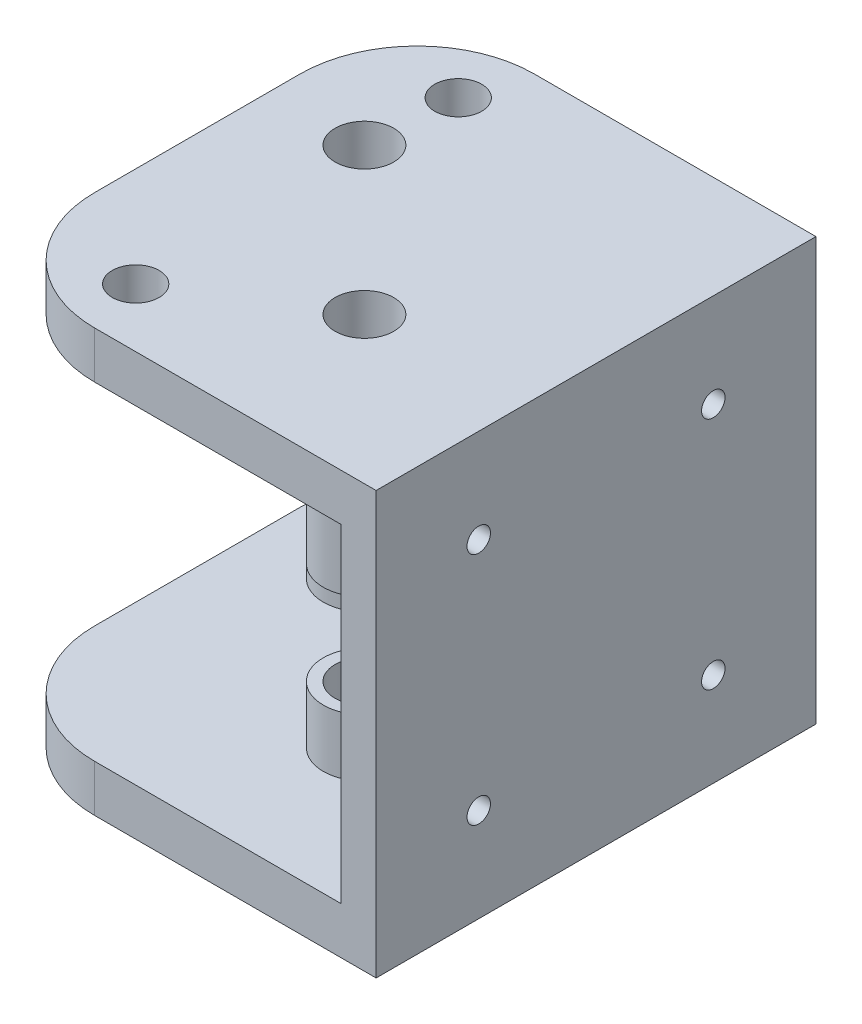
SolidWorks part; units mm, degrees
ref_plane "Front Plane" through (0, 0, 0) normal (0, 0, 1) x (1, 0, 0)
ref_plane "Top Plane" through (0, 0, 0) normal (0, 1, 0) x (1, 0, 0)
ref_plane "Right Plane" through (0, 0, 0) normal (1, 0, 0) x (0, 0, -1)
sketch "TopSketch1" plane through (0, 0, 0) normal (0, 1, 0) x (1, 0, 0)
  line L1 (0, 0) -> (34, 0)
  line L2 (0, 0) -> (0, 37.5)
  line L3 (0, 37.5) -> (34, 37.5)
  line L4 (34, 0) -> (34, 37.5)
  circle A0 centre (8.5, 32.5) radius 2
  circle A1 centre (8.5, 5) radius 2
  circle A2 centre (20.5, 12.5) radius 2.5
  circle A3 centre (8, 25) radius 2.5
  dimension "D7" = 4
  dimension "D8" = 5
  dimension "D2" = 12.5
  dimension "D3" = 12.5
  dimension "D4" = 5
  dimension "D5" = 5
  dimension "D10" = 37.5
  dimension "D9" = 12.5
  dimension "D12" = 13.5
  dimension "D6" = 25.5
  dimension "D11" = 8
  dimension "D13" = 12.5
extrude "Boss-Extrude1" add sketch "TopSketch1" along normal blind 4
sketch "TopLeftRiser" plane through (0, 0, 0) normal (0, -1, 0) x (1, 0, 0)
  line L0 (5.75, -27.681) -> (5.75, -37.5)
  line L1 (34, -37.5) -> (0, -37.5) construction
  line L2 (5.75, -37.5) -> (10.25, -37.5)
  line L3 (10.25, -37.5) -> (10.25, -27.681)
  arc A0 (10.25, -27.681) -> (5.75, -27.681) centre (8, -25) ccw
  circle A1 centre (8, -25) radius 2.5 construction
  circle A2 centre (8, -25) radius 2.5
  point P12 (8, -37.5)
  dimension "D1" = 7
  dimension "D2" = 4.5
extrude "TopLeftRiserBoss-Extrude2" add sketch "TopLeftRiser" along normal blind 4.9
sketch "TopRightRiser" plane through (0, 0, 0) normal (0, -1, 0) x (1, 0, 0)
  line L0 (18.25, -15.181) -> (18.25, -37.5)
  line L1 (34, -37.5) -> (10.25, -37.5) construction
  line L2 (18.25, -37.5) -> (22.75, -37.5)
  line L3 (22.75, -37.5) -> (22.75, -15.181)
  line L4 (5.75, -37.5) -> (10.25, -37.5) construction
  circle A0 centre (20.5, -12.5) radius 2.5
  circle A1 centre (20.5, -12.5) radius 2.5 construction
  arc A2 (22.75, -15.181) -> (18.25, -15.181) centre (20.5, -12.5) ccw
  arc A3 (10.25, -27.681) -> (5.75, -27.681) centre (8, -25) ccw construction
  point P15 (20.5, -37.5)
extrude "topRightRiserBoss-Extrude3" add sketch "TopRightRiser" along normal blind 14.4
sketch "MidWallSketch3" plane through (0, 0, 0) normal (0, -1, 0) x (1, 0, 0)
  line L1 (0, -34.5) -> (10.25, -34.5)
  line L2 (0, -34.5) -> (0, -37.5)
  line L3 (0, -37.5) -> (10.25, -37.5)
  line L4 (10.25, -34.5) -> (10.25, -37.5)
  line L5 (18.25, -34.5) -> (22.75, -34.5)
  line L6 (18.25, -34.5) -> (18.25, -37.5)
  line L7 (18.25, -37.5) -> (22.75, -37.5)
  line L8 (22.75, -34.5) -> (22.75, -37.5)
  line L9 (34, 0) -> (34, -37.5)
  line L10 (34, -37.5) -> (31, -37.5)
  line L11 (31, -37.5) -> (31, 0)
  line L14 (10.25, -37.5) -> (10.25, -27.681) construction
  line L15 (0, -37.5) -> (0, 0) construction
  line L16 (34, -37.5) -> (0, -37.5) construction
  line L17 (31, 0) -> (34, 0)
  line L19 (34, 0) -> (34, -37.5) construction
  line L20 (0, 0) -> (34, 0) construction
  line L21 (22.75, -37.5) -> (22.75, -15.181) construction
  line L22 (18.25, -15.181) -> (18.25, -37.5) construction
  dimension "D1" = 3
extrude "WallBoss-Extrude4" add sketch "MidWallSketch3" along normal blind 28
sketch "BottomSketch4" plane through (0, -28, 0) normal (0, -1, 0) x (1, 0, 0)
  line L0 (0, 0) -> (34, 0) construction
  line L1 (0, 0) -> (34, 0)
  line L2 (0, 0) -> (0, -37.5)
  line L3 (0, -37.5) -> (34, -37.5)
  line L4 (34, 0) -> (34, -37.5)
  line L5 (34, 0) -> (34, -37.5) construction
  line L6 (34, -37.5) -> (0, -37.5) construction
extrude "BottomBoss-Extrude5" add sketch "BottomSketch4" along normal blind 4
sketch "LowerLeftRiser" plane through (0, -28, 0) normal (0, 1, 0) x (1, 0, 0)
  line L0 (5.75, 27.681) -> (5.75, 34.5)
  line L1 (5.75, 34.5) -> (10.25, 34.5)
  line L2 (10.25, 34.5) -> (10.25, 27.681)
  line L3 (5.75, 34.5) -> (10.25, 34.5) construction
  line L4 (5.75, 27.681) -> (5.75, 34.5) construction
  line L5 (10.25, 34.5) -> (10.25, 27.681) construction
  circle A0 centre (8, 25) radius 2.5
  arc A1 (5.75, 27.681) -> (10.25, 27.681) centre (8, 25) ccw
  circle A2 centre (8, 25) radius 2.5 construction
  arc A3 (5.75, 27.681) -> (10.25, 27.681) centre (8, 25) ccw construction
extrude "LowerLeftRiserBoss-Extrude6" add sketch "LowerLeftRiser" along normal blind 14.4
sketch "LowerRightRiser" plane through (0, -28, 0) normal (0, 1, 0) x (1, 0, 0)
  line L0 (18.25, 15.181) -> (18.25, 34.5)
  line L1 (18.25, 34.5) -> (22.75, 34.5)
  line L2 (22.75, 34.5) -> (22.75, 15.181)
  line L3 (18.25, 34.5) -> (22.75, 34.5) construction
  line L4 (18.25, 15.181) -> (18.25, 34.5) construction
  line L5 (22.75, 34.5) -> (22.75, 15.181) construction
  circle A0 centre (20.5, 12.5) radius 2.5
  circle A1 centre (20.5, 12.5) radius 2.5 construction
  arc A2 (18.25, 15.181) -> (22.75, 15.181) centre (20.5, 12.5) ccw
  arc A3 (18.25, 15.181) -> (22.75, 15.181) centre (20.5, 12.5) ccw construction
extrude "LowerRightRiserBoss-Extrude7" add sketch "LowerRightRiser" along normal blind 4.9
fillet "Fillet1" radius 10 3 edges at (0, -30, 0) (0, 2, 0) (0, -14, -37.5)
sketch "GBMountingHolesSketch7" plane through (34, 0, 0) normal (1, 0, 0) x (0, 0, -1)
  line L0 (37.5, 4) -> (37.5, -32) construction
  line L1 (0, 4) -> (37.5, 4) construction
  line L2 (37.5, -32) -> (0, -32) construction
  line L3 (0, 4) -> (0, -32) construction
  circle A0 centre (8.75, -4) radius 1
  circle A1 centre (8.75, -24) radius 1
  circle A2 centre (28.75, -24) radius 1
  circle A3 centre (28.75, -4) radius 1
  dimension "D7" = 2
  dimension "D1" = 20
  dimension "D2" = 8.75
  dimension "D3" = 8
  dimension "D4" = 20
  dimension "D5" = 8
  dimension "D6" = 8.75
sketch "TopLeftInset" plane through (0, -4.9, 0) normal (0, -1, 0) x (1, 0, 0)
  line L0 (5.75, -27.681) -> (5.75, -34.5)
  line L1 (5.75, -34.5) -> (10.25, -34.5)
  line L2 (10.25, -34.5) -> (10.25, -27.681)
  line L3 (10.25, -34.5) -> (5.75, -34.5) construction
  line L4 (5.75, -34.5) -> (5.75, -27.681) construction
  line L5 (10.25, -27.681) -> (10.25, -34.5) construction
  arc A0 (5.75, -27.681) -> (10.25, -27.681) centre (8, -25) ccw
  arc A1 (10.25, -27.681) -> (5.75, -27.681) centre (8, -25) ccw construction
extrude "TopLeftInsetCut-Extrude1" cut sketch "TopLeftInset" against normal blind 1
sketch "TopRightInset" plane through (0, -14.4, 0) normal (0, -1, 0) x (1, 0, 0)
  line L0 (18.25, -15.181) -> (18.25, -34.5)
  line L1 (18.25, -34.5) -> (22.75, -34.5)
  line L2 (22.75, -34.5) -> (22.75, -15.181)
  line L3 (22.75, -34.5) -> (18.25, -34.5) construction
  line L4 (18.25, -34.5) -> (18.25, -15.181) construction
  line L5 (22.75, -15.181) -> (22.75, -34.5) construction
  arc A0 (18.25, -15.181) -> (22.75, -15.181) centre (20.5, -12.5) ccw
  arc A1 (22.75, -15.181) -> (18.25, -15.181) centre (20.5, -12.5) ccw construction
extrude "TopRightInsetCut-Extrude2" cut sketch "TopRightInset" against normal blind 1
sketch "LowerLeftInset" plane through (0, -13.6, 0) normal (0, 1, 0) x (1, 0, 0)
  line L0 (5.75, 27.681) -> (5.75, 34.5)
  line L1 (5.75, 34.5) -> (10.25, 34.5)
  line L2 (10.25, 34.5) -> (10.25, 27.681)
  line L3 (5.75, 34.5) -> (10.25, 34.5) construction
  line L4 (5.75, 27.681) -> (5.75, 34.5) construction
  line L5 (10.25, 34.5) -> (10.25, 27.681) construction
  arc A0 (10.25, 27.681) -> (5.75, 27.681) centre (8, 25) ccw
  arc A1 (5.75, 27.681) -> (10.25, 27.681) centre (8, 25) ccw construction
extrude "LowerLeftInsetCut-Extrude3" cut sketch "LowerLeftInset" against normal blind 1
sketch "LowerRightInset" plane through (0, -23.1, 0) normal (0, 1, 0) x (1, 0, 0)
  line L0 (18.25, 15.181) -> (18.25, 34.5)
  line L1 (18.25, 34.5) -> (22.75, 34.5)
  line L2 (22.75, 34.5) -> (22.75, 15.181)
  line L3 (18.25, 34.5) -> (22.75, 34.5) construction
  line L4 (18.25, 15.181) -> (18.25, 34.5) construction
  line L5 (22.75, 34.5) -> (22.75, 15.181) construction
  arc A2 (22.75, 15.181) -> (18.25, 15.181) centre (20.5, 12.5) ccw
  arc A3 (18.25, 15.181) -> (22.75, 15.181) centre (20.5, 12.5) ccw construction
extrude "LowerRightInsetCut-Extrude4" cut sketch "LowerRightInset" against normal blind 1
extrude "GBMountingHolesCut-Extrude5" cut sketch "GBMountingHolesSketch7" against normal blind 3
sketch "PushPinHoleSketch1" plane through (0, -32, 0) normal (0, -1, 0) x (1, 0, 0)
  circle A0 centre (20.5, -12.5) radius 1
  circle A1 centre (8, -25) radius 1
  circle A2 centre (8, -25) radius 2.5 construction
  circle A3 centre (20.5, -12.5) radius 2.5 construction
  dimension "D1" = 2
extrude "PushPinHoleCut-Extrude1" cut sketch "PushPinHoleSketch1" against normal through all
sketch "BottomLeftMountHoleAccessSketch1" plane through (5.75, 0, 0) normal (-1, 0, 0) x (0, 0, 1)
  circle A0 centre (-28.75, -24) radius 1
  dimension "D1" = 2
extrude "BottomLeftMountHoleAccessCut-Extrude2" cut sketch "BottomLeftMountHoleAccessSketch1" against normal blind 15 and the other way blind 10
sketch "TopLeftMountHoleAccessSketch2" plane through (18.25, 0, 0) normal (-1, 0, 0) x (0, 0, 1)
  circle A0 centre (-28.75, -4) radius 1
  circle A1 centre (-28.75, -24) radius 1 construction
extrude "TopLeftMountHoleAccessCut-Extrude3" cut sketch "TopLeftMountHoleAccessSketch2" against normal blind 5 and the other way through all
equation "\"GABDepth\"= \"GABDistanceFromBackToFirstPulley\" + \"GABPulleyDDistanceBetween\" + \"GABDistanceFromPulleyToFront\""
equation "\"GABWidth\"= \"StandardWallThickness\" + \"GABDistanceFromLSideToPulley\" + \"GABPulleyWDistanceBetween\" + \"GABDistanceFromPulleyToRSide\""
equation "\"GABLowerHeight\"= 4mm"
equation "\"GABUpperHeight\"= 4mm"
equation "\"GABMidWallHeight\"= 28mm'Must equal 28 or changes alignment"
equation "\"StandardWallThickness\"= 3mm"
equation "\"GABMidShortRiserHeight\"= \"GABMidWallHeight\" / 2 - \"20TGT2PulleyWidth\"'Equals 5.3"
equation "\"LinearGBMountHolesXDistance\"= 20mm'Spec"
equation "\"GABHeight\"= \"GABLowerHeight\" + \"GABMidWallHeight\" + \"GABUpperHeight\""
equation "\"GBMountingHoleDiameter\"= 2mm"
equation "\"GABMidLongRiserHeight\"= \"GABMidWallHeight\" - \"GABMidShortRiserHeight\" - \"20TGT2PulleyWidth\"'Equals 14"
equation "\"GABLRClampHoleOffsetFromSide\"= 5mm"
equation "\"GABDistanceFromBackToFirstPulley\"= 13.5mm"
equation "\"GABPulleyDDistanceBetween\"= 12.5mm'From the100"
equation "\"GABPulleyWDistanceBetween\"= 14.5mm'From the100"
equation "\"GABDistanceFromPulleyToFront\"= 8mm"
equation "\"GABDistanceFromLSideToPulley\"= 9.5mm + \"StandardWallThickness\""
equation "\"GABDistanceFromPulleyToRSide\"= 7.5mm"
equation "\"GABDistanceToFrontClampHoles\"= 8.5mm"
equation "\"SteelShaft5mmHoleDiameter\"= 5mm"
equation "\"20TGT2PulleyWidth\"= 8.7mm'The STL of the Pulley in the diagram is a bit larger"
equation "\"7mmx1mmSpacerDiameter\"= 7mm"
equation "\"7mmx1mmSpacerHeight\"= 1mm"
equation "\"GABRiserBossOffset\" = 0.4mm'Aligns Pulleys inside edges to be 2.5mm (.5mm apart top to bottom)"
equation "\"D2@TopSketch1\" = \"GABPulleyDDistanceBetween\""
equation "\"D3@TopSketch1\" = \"GABPulleyDDistanceBetween\""
equation "\"D4@TopSketch1\" = \"GABLRClampHoleOffsetFromSide\""
equation "\"D5@TopSketch1\" = \"GABLRClampHoleOffsetFromSide\""
equation "\"D8@TopSketch1\" = \"SteelShaft5mmHoleDiameter\""
equation "\"D10@TopSketch1\" = \"GABWidth\""
equation "\"D9@TopSketch1\" = \"GABDistanceFromLSideToPulley\""
equation "\"D12@TopSketch1\"=\"GABDistanceFromBackToFirstPulley\""
equation "\"D1@Boss-Extrude1\"=\"GABUpperHeight\""
equation "\"D1@TopLeftRiser\" = \"7mmx1mmSpacerDiameter\""
equation "\"D1@TopLeftRiserBoss-Extrude2\" = \"GABMidShortRiserHeight\" - \"GABRiserBossOffset\""
equation "\"D1@topRightRiserBoss-Extrude3\" = \"GABMidLongRiserHeight\" + \"GABRiserBossOffset\""
equation "\"D1@WallBoss-Extrude4\" = \"GABMidWallHeight\""
equation "\"D1@BottomBoss-Extrude5\" = \"GABLowerHeight\""
equation "\"D1@LowerLeftRiserBoss-Extrude6\" = \"GABMidLongRiserHeight\" + \"GABRiserBossOffset\""
equation "\"D1@LowerRightRiserBoss-Extrude7\" = \"GABMidShortRiserHeight\" - \"GABRiserBossOffset\""
equation "\"D1@GBMountingHolesSketch7\" = \"LinearGBMountHolesXDistance\""
equation "\"D2@GBMountingHolesSketch7\" =  ( \"GABWidth\" - \"LinearGBMountHolesXDistance\" )  / 2"
equation "\"D3@GBMountingHolesSketch7\" =  ( \"GABHeight\" - \"LinearGBMountHolesXDistance\" )  / 2"
equation "\"D4@GBMountingHolesSketch7\"=\"LinearGBMountHolesYDistance\""
equation "\"D7@GBMountingHolesSketch7\"=\"GBMountingHoleDiameter\""
equation "\"D1@TopLeftInsetCut-Extrude1\" = \"7mmx1mmSpacerHeight\""
equation "\"D1@TopRightInsetCut-Extrude2\" = \"7mmx1mmSpacerHeight\""
equation "\"D1@LowerLeftInsetCut-Extrude3\" = \"7mmx1mmSpacerHeight\""
equation "\"D1@LowerRightInsetCut-Extrude4\" = \"7mmx1mmSpacerHeight\""
equation "\"D1@GBMountingHolesCut-Extrude5\" = \"StandardWallThickness\""
equation "\"D6@TopSketch1\"=\"GABDepth\" - \"GABDistanceToFrontClampHoles\""
equation "\"D11@TopSketch1\"=\"GABDistanceFromPulleyToFront\""
equation "\"LinearGBMountHolesYDistance\"= 20mm'Spec"
equation "\"StealPinPushHoleDiameter\"= 2mm"
equation "\"D1@PushPinHoleSketch1\" = \"StealPinPushHoleDiameter\""
equation "\"M3HeatInsertHoleDiameter\"= 4mm'Spec"
equation "\"D7@TopSketch1\"=\"M3HeatInsertHoleDiameter\""
